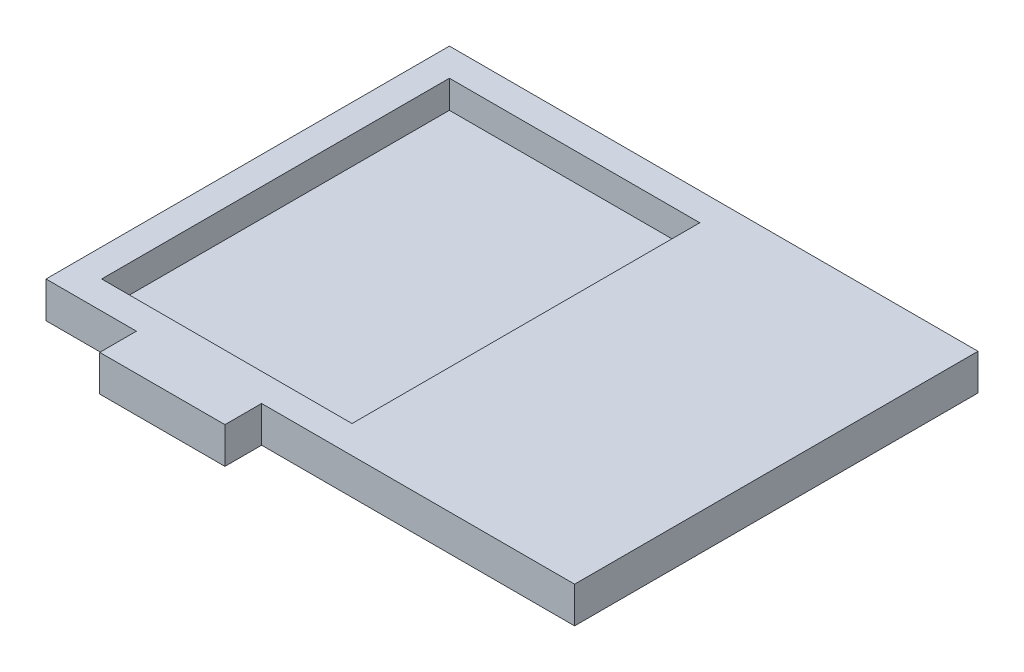
SolidWorks part; units mm, degrees
material "Natural Rubber"
ref_plane "Front Plane" through (0, 0, 0) normal (0, 0, 1) x (1, 0, 0)
ref_plane "Top Plane" through (0, 0, 0) normal (0, 1, 0) x (1, 0, 0)
ref_plane "Right Plane" through (0, 0, 0) normal (1, 0, 0) x (0, 0, -1)
sketch "Sketch1" plane through (0, 0, 0) normal (0, 1, 0) x (1, 0, 0)
  line L0 (45, 0) -> (45, -23.1837) construction
  line L1 (0, 0) -> (90, 0)
  line L2 (0, 0) -> (0, 125)
  line L3 (0, 125) -> (90, 125)
  line L4 (90, 0) -> (90, 125)
  line L5 (-10, -10) -> (180, -10)
  line L6 (-10, -10) -> (-10, 135)
  line L7 (-10, 135) -> (180, 135)
  line L8 (180, -10) -> (180, 135)
  line L9 (22.5, -10) -> (67.5, -10)
  line L10 (22.5, -10) -> (22.5, -23.1837)
  line L11 (22.5, -23.1837) -> (67.5, -23.1837)
  line L12 (67.5, -10) -> (67.5, -23.1837)
  point P16 (45, -23.1837)
  dimension "D1" = 90
  dimension "D2" = 125
  dimension "D3" = 10
  dimension "D4" = 10
  dimension "D5" = 90
  dimension "D6" = 10
  dimension "D7" = 45
extrude "Boss-Extrude1" add sketch "Sketch1" against normal blind 3 contours L1 L4 L3 L2 | L5 L8 L7 L6 L4 L1 L2 L3 | L2 L1 L4 L3 | L6 L5 L8 L7 | L10 L9 L12 L11 region at (45, 0, -62.5) region at (112.6074, 0, -62.5)
extrude "Boss-Extrude2" add sketch "Sketch1<3>" along normal blind 10 contours L4 L1 L9 L5 L8 L7 L6 L2 L3 | L0 L5 L10 L11 | L9 L0 L11 L12 region at (112.6074, 0, -62.5) region at (56.25, 0, 16.5918) region at (33.75, 0, 16.5918)
sketch "Sketch1<3>" plane through (0, 0, 0) normal (0, 1, 0) x (1, 0, 0) same geometry as "Sketch1"
